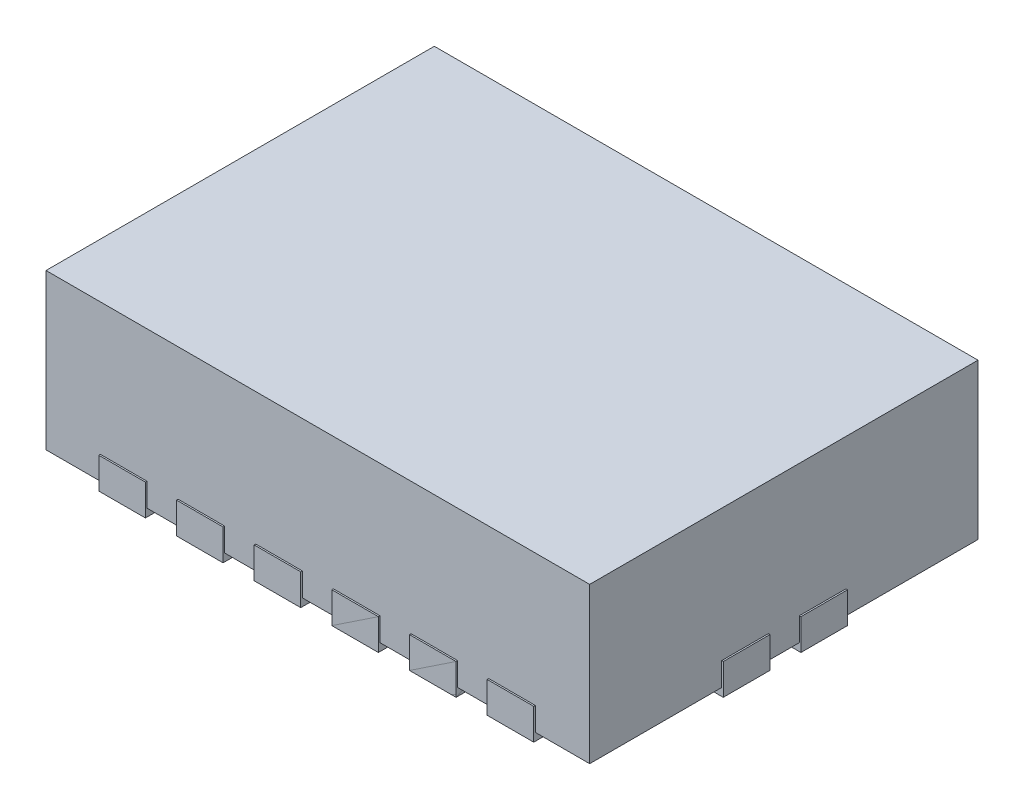
SolidWorks part; units mm, degrees
ref_plane "Front Plane" through (0, 0, 0) normal (0, 0, 1) x (1, 0, 0)
ref_plane "Top Plane" through (0, 0, 0) normal (0, 1, 0) x (1, 0, 0)
ref_plane "Right Plane" through (0, 0, 0) normal (1, 0, 0) x (0, 0, -1)
sketch "Sketch1" plane through (0, 0, 0) normal (0, 1, 0) x (1, 0, 0)
  line L1 (0, 0) -> (3.5, 0)
  line L2 (0, 0) -> (0, 2.5)
  line L3 (0, 2.5) -> (3.5, 2.5)
  line L4 (3.5, 0) -> (3.5, 2.5)
  dimension "D1" = 3.5
  dimension "D2" = 2.5
extrude "Boss-Extrude1" add sketch "Sketch1" along normal blind 1
sketch "Sketch2" plane through (0, 0, 0) normal (0, -1, 0) x (1, 0, 0)
  line L0 (2.15, 0.01) -> (2.15, -0.4)
  line L1 (1.85, 0.01) -> (2.15, 0.01)
  line L7 (1.85, 0.01) -> (1.85, -0.4)
  arc A0 (1.85, -0.4) -> (2.15, -0.4) centre (2, -0.3375) ccw
extrude "Boss-Extrude2" add sketch "Sketch2" against normal blind 0.2 from offset 0.05 separate body
pattern_linear "LPattern1" count 3 spacing 0.5 along (1, 0, 0) count 4 spacing 0.5 along (-1, 0, 0) of "Boss-Extrude2"
ref_plane "Plane1" through (0, 0, -1.25) normal (0, 0, 1) x (1, 0, 0)
sketch "Sketch4" plane through (0, 0, 0) normal (0, -1, 0) x (1, 0, 0)
  line L0 (1.35, -2.51) -> (1.35, -2.1)
  line L1 (1.65, -2.51) -> (1.35, -2.51)
  line L2 (1.65, -2.51) -> (1.65, -2.1)
  arc A0 (1.65, -2.1) -> (1.35, -2.1) centre (1.5, -2.1625) ccw
  point P9 (0, 0)
extrude "Boss-Extrude3" add sketch "Sketch4" against normal blind 0.2 from offset 0.05 separate body
pattern_linear "LPattern2" count 3 spacing 0.5 along (-1, 0, 0) count 4 spacing 0.5 along (1, 0, 0) of "Boss-Extrude3"
sketch "Sketch5" plane through (0, 0, 0) normal (0, -1, 0) x (1, 0, 0)
  line L2 (-0.01, -0.85) -> (0.4, -0.85)
  line L3 (-0.01, -1.15) -> (-0.01, -0.85)
  line L4 (-0.01, -1.15) -> (0.4, -1.15)
  arc A0 (0.4, -1.15) -> (0.4, -0.85) centre (0.3375, -1) ccw
extrude "Boss-Extrude4" add sketch "Sketch5" against normal blind 0.2 from offset 0.05 separate body
pattern_linear "LPattern3" count 2 spacing 0.5 along (0, 0, -1) of "Boss-Extrude4"
ref_plane "Plane2" through (1.75, 0, 0) normal (1, 0, 0) x (0, 0, -1)
mirror "Mirror7" about plane through (1.75, 0, 0) normal (1, 0, 0) of "LPattern3", "Boss-Extrude4"
